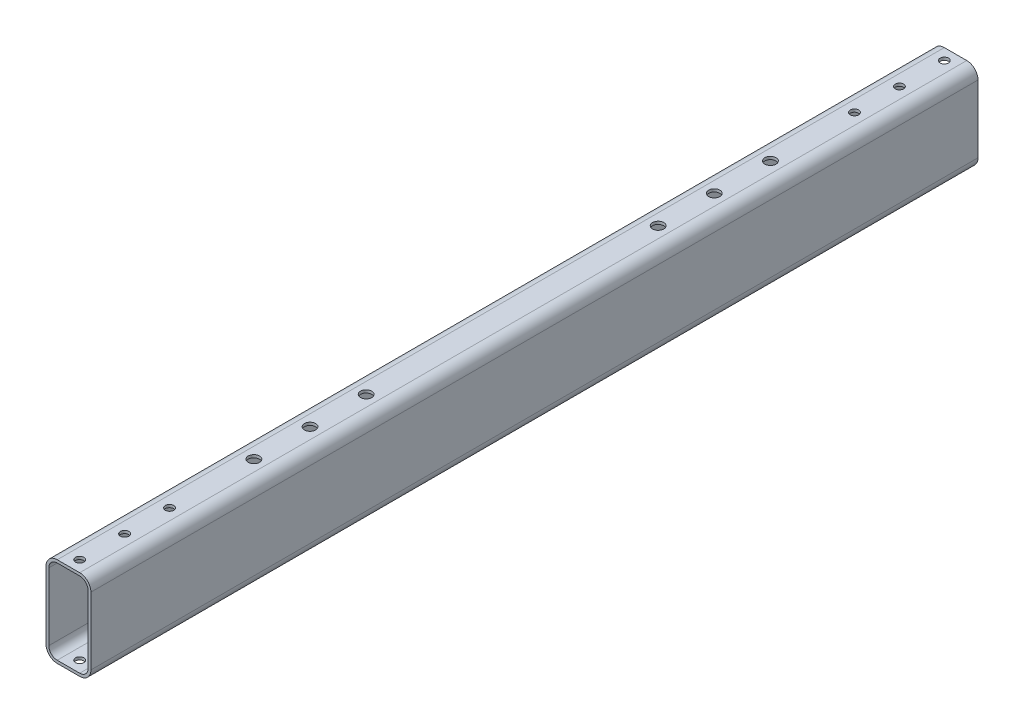
SolidWorks part; units mm, degrees
material "6061-T6 (SS)"
ref_plane "Front Plane" through (0, 0, 0) normal (0, 0, 1) x (1, 0, 0)
ref_plane "Top Plane" through (0, 0, 0) normal (0, 1, 0) x (1, 0, 0)
ref_plane "Right Plane" through (0, 0, 0) normal (1, 0, 0) x (0, 0, -1)
sketch "Sketch1" plane through (0, 0, 0) normal (0, 0, 1) x (1, 0, 0)
  line L1 (-6.35, -25.4) -> (6.35, -25.4)
  line L2 (-12.7, -19.05) -> (-12.7, 19.05)
  line L3 (-6.35, 25.4) -> (6.35, 25.4)
  line L4 (12.7, -19.05) -> (12.7, 19.05)
  line L5 (-12.7, -25.4) -> (12.7, 25.4) construction
  line L6 (-12.7, 25.4) -> (12.7, -25.4) construction
  arc A0 (-12.7, -19.05) -> (-6.35, -25.4) centre (-6.35, -19.05) ccw
  arc A1 (6.35, -25.4) -> (12.7, -19.05) centre (6.35, -19.05) ccw
  arc A2 (6.35, 25.4) -> (12.7, 19.05) centre (6.35, 19.05) cw
  arc A3 (-12.7, 19.05) -> (-6.35, 25.4) centre (-6.35, 19.05) cw
  point P0 (0, 0)
  dimension "D3" = 6.35
  dimension "D1" = 50.8
  dimension "D2" = 25.4
extrude "Extrude-Thin1" add sketch "Sketch1" along normal blind 501.65 thin thin type one direction reverse wall 1.5875
hole_wizard "3/16 (0.1875) Diameter Hole1" positions "3DSketch1" profile "Sketch3" hole size "3/16" standard "ANSI Inch" end condition through all
sketch3d "3DSketch1"
  line L1 (6.35, 25.4, 0) -> (-6.35, 25.4, 0) construction
  line L6 (0, 25.4, 501.65) -> (0, 25.4, 0) construction
  line L7 (6.35, 25.4, 501.65) -> (-6.35, 25.4, 501.65) construction
  point P57 (0, 25.4, 6.35)
  point P59 (0, 25.4, 31.75)
  point P61 (0, 25.4, 57.15)
  point P63 (0, 25.4, 469.9)
  point P65 (0, 25.4, 444.5)
  point P67 (0, 25.4, 495.3)
  dimension "D1" = 25.4
  dimension "D2" = 25.4
  dimension "D3" = 6.35
  dimension "D4" = 25.4
  dimension "D5" = 25.4
  dimension "D6" = 6.35
sketch "Sketch3" plane through (0, 25.4, 495.3) normal (1, 0, 0) x (0, 0, 1)
  line L0 (0, 0) -> (0, 50.8)
  line L1 (0, 50.8) -> (2.3812, 50.8)
  line L2 (2.3812, 50.8) -> (2.3812, 0)
  line L5 (2.3812, 0) -> (0, 0)
  line L11 (0, -6.35) -> (0, 107.95) construction
  dimension "Thru Hole Dia." = 4.7625
  dimension "Thru Hole Depth" = 50.8
hole_wizard "3/16 (0.195) Diameter Hole1" positions "Sketch4" profile "Sketch5" hole size "3/16" standard "ANSI Inch" end condition up to next
sketch "Sketch4" plane through (0, -25.4, 0) normal (0, -1, 0) x (-1, 0, 0)
  point P74 (-3.175, -85.725)
  point P78 (3.175, -111.125)
  point P81 (-3.175, -136.525)
  point P84 (3.175, -161.925)
  point P87 (-3.175, -187.325)
  point P90 (3.175, -212.725)
  point P93 (-3.175, -238.125)
  point P96 (3.175, -263.525)
  point P99 (-3.175, -288.925)
  point P102 (3.175, -314.325)
  point P105 (-3.175, -339.725)
  point P108 (3.175, -365.125)
  point P111 (3.175, -415.925)
  point P114 (-3.175, -390.525)
  point P118 (-1.5244, -83.8788)
  point P119 (-3.175, -85.725)
sketch "Sketch5" plane through (3.175, -25.4, 85.725) normal (1, 0, 0) x (0, 0, -1)
  line L0 (0, 0) -> (0, 1.5875)
  line L1 (0, 1.5875) -> (2.4765, 1.5875)
  line L2 (2.4765, 1.5875) -> (2.4765, 0)
  line L5 (2.4765, 0) -> (0, 0)
  line L11 (0, -6.35) -> (0, 107.95) construction
  dimension "Thru Hole Dia." = 4.953
  dimension "Thru Hole Depth" = 1.5875
hole_wizard "1/4 (0.25) Diameter Hole1" positions "Sketch6" profile "Sketch7" hole size "1/4" standard "ANSI Inch"
sketch "Sketch6" plane through (0, 25.4, 0) normal (0, 1, 0) x (1, 0, 0)
  point P0 (0, -104.6752)
  point P3 (0, -136.4252)
  point P6 (0, -168.1752)
  point P9 (0, -396.8)
  point P12 (0, -365.05)
  point P15 (0, -333.3)
sketch "Sketch7" plane through (0, 25.4, 104.6752) normal (1, 0, 0) x (0, 0, 1)
  line L0 (0, 0) -> (0, 27.3077)
  line L1 (0, 27.3077) -> (3.175, 25.4)
  line L2 (3.175, 25.4) -> (3.175, 0)
  line L5 (3.175, 0) -> (0, 0)
  line L10 (0, 27.3077) -> (-3.175, 25.4) construction
  line L11 (0, -6.35) -> (0, 107.95) construction
  dimension "Hole Dia." = 6.35
  dimension "Hole Depth" = 25.4
  dimension "Drill Angle" = 118
